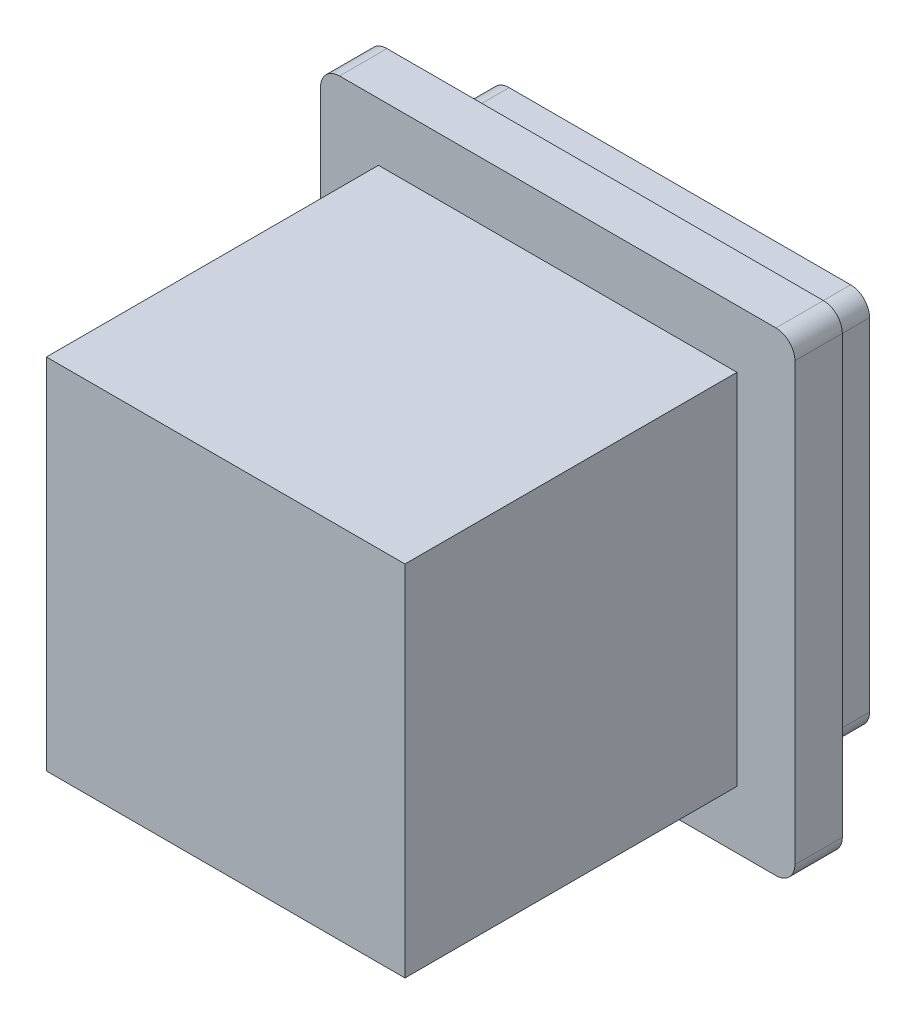
SolidWorks part; units mm, degrees
ref_plane "Front Plane" through (0, 0, 0) normal (0, 0, 1) x (1, 0, 0)
ref_plane "Top Plane" through (0, 0, 0) normal (0, 1, 0) x (1, 0, 0)
ref_plane "Right Plane" through (0, 0, 0) normal (1, 0, 0) x (0, 0, -1)
sketch "Sketch1" plane through (0, 0, 0) normal (0, 0, 1) x (1, 0, 0)
  line L1 (0, 0) -> (25.4, 0)
  line L2 (0, 0) -> (0, 25.4)
  line L3 (0, 25.4) -> (25.4, 25.4)
  line L4 (25.4, 0) -> (25.4, 25.4)
  dimension "D1" = 25.4
  dimension "D2" = 25.4
extrude "Boss-Extrude1" add sketch "Sketch1" along normal blind 5
sketch "Sketch2" plane through (0, 0, 5) normal (0, 0, 1) x (1, 0, 0)
  line L0 (0, 25.4) -> (0, 0) construction
  line L1 (0.7, 24.7) -> (24.7, 24.7)
  line L2 (0.7, 24.7) -> (0.7, 0.7)
  line L3 (0.7, 0.7) -> (24.7, 0.7)
  line L4 (24.7, 24.7) -> (24.7, 0.7)
  line L5 (25.4, 25.4) -> (0, 25.4) construction
  point P4 (0.7, 12.7)
  point P7 (0, 12.7)
  point P8 (12.7, 24.7)
  point P11 (12.7, 25.4)
  dimension "D1" = 0
  dimension "D2" = 0
  dimension "D3" = 24
  dimension "D4" = 24
fillet "Fillet1" radius 1.27 4 edges at (0, 0, 2.5) (25.4, 0, 2.5) (0, 25.4, 2.5) (25.4, 25.4, 2.5)
sketch "Sketch3" plane through (0, 0, 0) normal (0, 0, -1) x (-1, 0, 0)
  line L0 (-25.4, 1.27) -> (-25.4, 24.13) construction
  line L1 (-19.05, 21.59) -> (-16.51, 21.59)
  line L2 (-19.05, 21.59) -> (-19.05, 13.97)
  line L3 (-19.05, 13.97) -> (-16.51, 13.97)
  line L4 (-16.51, 21.59) -> (-16.51, 13.97)
  line L5 (-24.13, 25.4) -> (-1.27, 25.4) construction
  line L6 (-8.89, 21.59) -> (-6.35, 21.59)
  line L7 (-8.89, 21.59) -> (-8.89, 13.97)
  line L8 (-8.89, 13.97) -> (-6.35, 13.97)
  line L9 (-6.35, 21.59) -> (-6.35, 13.97)
  line L10 (0, 24.13) -> (0, 1.27) construction
  line L11 (-13.625, 1.4094) -> (-13.625, 7.8295) construction
  line L12 (-16.165, 5.08) -> (-16.165, 8.636)
  line L13 (-11.085, 5.08) -> (-11.085, 8.636)
  line L14 (-16.165, 5.08) -> (-11.085, 5.08)
  line L15 (-1.27, 0) -> (-24.13, 0) construction
  arc A1 (-11.085, 8.636) -> (-16.165, 8.636) centre (-13.625, 7.8295) ccw
  point P16 (-13.5, 5.1417)
  dimension "D10" = 2.665
  dimension "D1" = 2.54
  dimension "D2" = 7.62
  dimension "D3" = 6.35
  dimension "D4" = 2.54
  dimension "D5" = 7.62
  dimension "D6" = 3.81
  dimension "D7" = 6.35
  dimension "D8" = 3.81
  dimension "D9" = 5.08
  dimension "D11" = 3.556
  dimension "D12" = 11.085
  dimension "D13" = 5.08
extrude "Cut-Extrude1" cut sketch "Sketch3" against normal blind 2.54
sketch "Sketch4" plane through (0, 0, 5) normal (0, 0, 1) x (1, 0, 0)
  line L0 (24.7, 24.7) -> (24.7, 0.7) construction
  line L1 (-3.175, 28.575) -> (28.575, 28.575)
  line L2 (-3.175, 28.575) -> (-3.175, -3.175)
  line L3 (-3.175, -3.175) -> (28.575, -3.175)
  line L4 (28.575, 28.575) -> (28.575, -3.175)
  line L5 (-3.175, 28.575) -> (28.575, -3.175) construction
  line L6 (-3.175, -3.175) -> (28.575, 28.575) construction
  line L7 (0.7, 24.7) -> (24.7, 24.7) construction
  point P0 (12.7, 12.7)
  point P7 (24.7, 12.7)
  point P10 (12.7, 24.7)
  dimension "D1" = 31.75
  dimension "D2" = 31.75
extrude "Boss-Extrude2" add sketch "Sketch4" along normal blind 3.175
extrude "Boss-Extrude3" add sketch "Sketch2" along normal blind 25.4
fillet "Fillet2" radius 1.27 4 edges at (28.575, -3.175, 6.5875) (-3.175, -3.175, 6.5875) (-3.175, 28.575, 6.5875) (28.575, 28.575, 6.5875)
